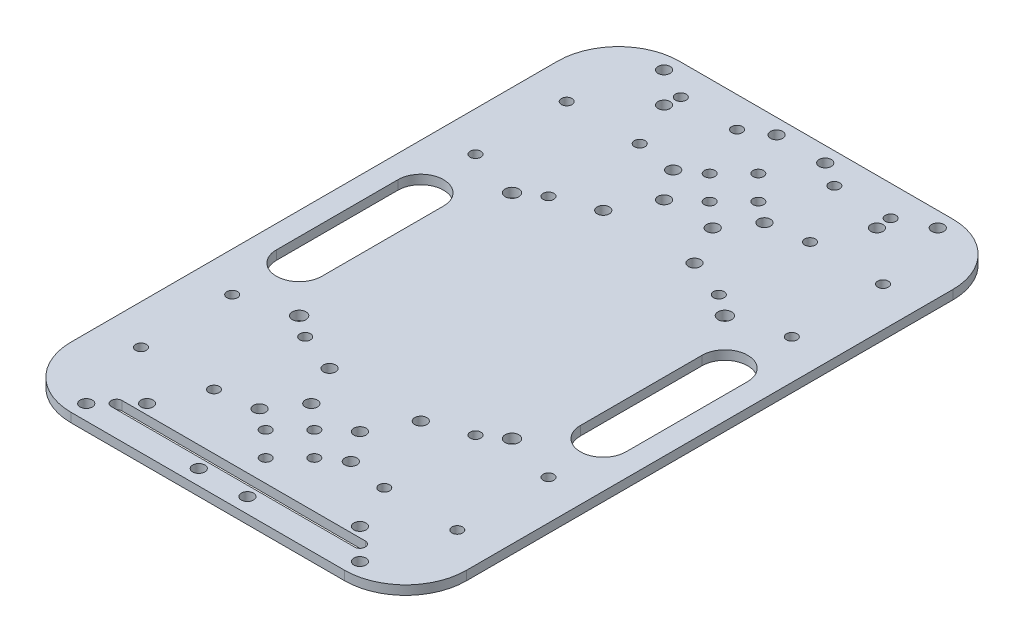
SolidWorks part; units mm, degrees
ref_plane "前视基准面" through (0, 0, 0) normal (0, 0, 1) x (1, 0, 0)
ref_plane "上视基准面" through (0, 0, 0) normal (0, 1, 0) x (1, 0, 0)
ref_plane "右视基准面" through (0, 0, 0) normal (1, 0, 0) x (0, 0, -1)
other "Configuration Table"
sketch "草图1" plane through (0, 0, 0) normal (0, 1, 0) x (1, 0, 0)
  line L0 (-40, -90) -> (40, -90) construction
  line L1 (-65, -100) -> (65, -100)
  line L2 (-65, -100) -> (-65, 100)
  line L3 (-65, 100) -> (65, 100)
  line L4 (65, -100) -> (65, 100)
  line L5 (-65, -100) -> (65, 100) construction
  line L6 (-65, 100) -> (65, -100) construction
  line L7 (-40, -88.25) -> (40, -88.25)
  line L8 (-40, -91.75) -> (40, -91.75)
  line L9 (50, -20) -> (50, 20) construction
  line L10 (42.5, -20) -> (42.5, 20)
  line L11 (57.5, -20) -> (57.5, 20)
  line L12 (-50, -20) -> (-50, 20) construction
  line L13 (-57.5, -20) -> (-57.5, 20)
  line L14 (-42.5, -20) -> (-42.5, 20)
  line L15 (0, 100) -> (0, -100) construction
  line L16 (-65, 0) -> (65, 0) construction
  circle A0 centre (52, -70) radius 1.75
  circle A1 centre (52, -40) radius 1.75
  circle A2 centre (28, -40) radius 1.75
  circle A3 centre (28, -70) radius 1.75
  circle A4 centre (52, 40) radius 1.75
  circle A5 centre (52, 70) radius 1.75
  circle A6 centre (28, 70) radius 1.75
  circle A7 centre (28, 40) radius 1.75
  circle A8 centre (-28, 40) radius 1.75
  circle A9 centre (-28, 70) radius 1.75
  circle A10 centre (-52, 70) radius 1.75
  circle A11 centre (-52, 40) radius 1.75
  circle A12 centre (-28, -70) radius 1.75
  circle A13 centre (-28, -40) radius 1.75
  circle A14 centre (-52, -40) radius 1.75
  circle A15 centre (-52, -70) radius 1.75
  circle A16 centre (35, -35) radius 2.25
  circle A17 centre (-35, -35) radius 2.25
  circle A18 centre (-35, 35) radius 2.25
  circle A19 centre (35, 35) radius 2.25
  circle A20 centre (16, 90) radius 1.75
  circle A21 centre (-16, 90) radius 1.75
  circle A22 centre (-34.5, 90) radius 1.75
  circle A25 centre (34.5, 90) radius 1.75
  circle A26 centre (-8, 73) radius 1.75
  circle A29 centre (0, 65) radius 1.75
  circle A31 centre (0, 81) radius 1.75
  circle A34 centre (8, 73) radius 1.75
  circle A35 centre (-8, -73) radius 1.75
  circle A36 centre (0, -81) radius 1.75
  circle A37 centre (0, -65) radius 1.75
  circle A38 centre (8, -73) radius 1.75
  arc A39 (-40, -88.25) -> (-40, -91.75) centre (-40, -90) ccw
  arc A40 (40, -91.75) -> (40, -88.25) centre (40, -90) ccw
  arc A41 (42.5, -20) -> (57.5, -20) centre (50, -20) ccw
  arc A42 (57.5, 20) -> (42.5, 20) centre (50, 20) ccw
  arc A43 (-57.5, -20) -> (-42.5, -20) centre (-50, -20) ccw
  arc A44 (-42.5, 20) -> (-57.5, 20) centre (-50, 20) ccw
  circle A45 centre (15, 45) radius 2
  circle A46 centre (-15, 45) radius 2
  circle A47 centre (-15, 68) radius 2
  circle A48 centre (15, 68) radius 2
  circle A53 centre (15, -68) radius 2
  circle A54 centre (-15, -68) radius 2
  circle A55 centre (-15, -45) radius 2
  circle A56 centre (15, -45) radius 2
  circle A57 centre (35, 85) radius 2
  circle A58 centre (-35, 85) radius 2
  circle A59 centre (35, -85) radius 2
  circle A60 centre (-35, -85) radius 2
  circle A61 centre (8, -58) radius 2
  circle A62 centre (8, -95) radius 2
  circle A63 centre (45, -95) radius 2
  circle A64 centre (-45, -95) radius 2
  circle A65 centre (-8, -95) radius 2
  circle A66 centre (-8, -58) radius 2
  circle A67 centre (45, 95) radius 2
  circle A68 centre (8, 95) radius 2
  circle A69 centre (-8, 95) radius 2
  circle A70 centre (-45, 95) radius 2
  circle A71 centre (8, 58) radius 2
  circle A72 centre (-8, 58) radius 2
  point P0 (0, 0)
  point P77 (0, -90)
  point P91 (50, 0)
  point P99 (-50, 0)
  dimension "D3" = 3.5
  dimension "D4" = 3.5
  dimension "D5" = 3.5
  dimension "D6" = 3.5
  dimension "D12" = 4.5
  dimension "D24" = 3.5
  dimension "D25" = 3.5
  dimension "D26" = 3.5
  dimension "D27" = 3.5
  dimension "D32" = 3.5
  dimension "D33" = 3.5
  dimension "D34" = 3.5
  dimension "D35" = 3.5
  dimension "D40" = 4.5
  dimension "D41" = 4.5
  dimension "D42" = 4.5
  dimension "D43" = 3.5
  dimension "D44" = 3.5
  dimension "D45" = 3.5
  dimension "D46" = 3.5
  dimension "D63" = 3.5
  dimension "D64" = 3.5
  dimension "D65" = 3.5
  dimension "D66" = 3.5
  dimension "D75" = 3.5
  dimension "D76" = 3.5
  dimension "D77" = 3.5
  dimension "D78" = 3.5
  dimension "D87" = 3.5
  dimension "D88" = 3.5
  dimension "D89" = 3.5
  dimension "D90" = 3.5
  dimension "D102" = 80
  dimension "D111" = 4
  dimension "D112" = 4
  dimension "D113" = 4
  dimension "D114" = 4
  dimension "D129" = 4
  dimension "D130" = 4
  dimension "D131" = 4
  dimension "D132" = 4
  dimension "D135" = 4
  dimension "D136" = 4
  dimension "D141" = 4
  dimension "D142" = 4
  dimension "D147" = 4
  dimension "D148" = 4
  dimension "D149" = 4
  dimension "D1" = 130
  dimension "D2" = 200
  dimension "D7" = 24
  dimension "D8" = 24
  dimension "D9" = 30
  dimension "D10" = 30
  dimension "D11" = 13
  dimension "D13" = 70
  dimension "D14" = 70
  dimension "D15" = 70
  dimension "D16" = 70
  dimension "D17" = 30
  dimension "D18" = 0
  dimension "D19" = 0
  dimension "D20" = 30
  dimension "D21" = 13
  dimension "D22" = 0
  dimension "D23" = 24
  dimension "D28" = 0
  dimension "D29" = 0
  dimension "D30" = 30
  dimension "D31" = 0
  dimension "D36" = 35
  dimension "D37" = 0
  dimension "D38" = 35
  dimension "D39" = 0
  dimension "D47" = 24
  dimension "D48" = 30
  dimension "D49" = 30
  dimension "D50" = 13
  dimension "D51" = 0
  dimension "D52" = 0
  dimension "D53" = 0
  dimension "D54" = 0
  dimension "D55" = 30
  dimension "D56" = 13
  dimension "D57" = 0
  dimension "D58" = 24
  dimension "D59" = 30
  dimension "D60" = 0
  dimension "D61" = 0
  dimension "D62" = 0
  dimension "D67" = 32
  dimension "D68" = 69
  dimension "D69" = 10
  dimension "D70" = 10
  dimension "D71" = 16
  dimension "D72" = 34.5
  dimension "D73" = 0
  dimension "D74" = 0
  dimension "D79" = 16
  dimension "D80" = 16
  dimension "D81" = 0
  dimension "D82" = 0
  dimension "D83" = 8
  dimension "D84" = 8
  dimension "D85" = 65
  dimension "D86" = 8
  dimension "D91" = 16
  dimension "D92" = 16
  dimension "D93" = 8
  dimension "D94" = 8
  dimension "D95" = 0
  dimension "D96" = 8
  dimension "D97" = 65
  dimension "D98" = 0
  dimension "D99" = 3.5
  dimension "D100" = 0
  dimension "D101" = 10
  dimension "D103" = 0
  dimension "D104" = 40
  dimension "D105" = 15
  dimension "D106" = 15
  dimension "D107" = 0
  dimension "D108" = 15
  dimension "D109" = 40
  dimension "D110" = 15
  dimension "D115" = 30
  dimension "D116" = 0
  dimension "D117" = 0
  dimension "D118" = 23
  dimension "D119" = 0
  dimension "D120" = 15
  dimension "D121" = 45
  dimension "D122" = 0
  dimension "D123" = 30
  dimension "D124" = 23
  dimension "D125" = 45
  dimension "D126" = 0
  dimension "D127" = 0
  dimension "D128" = 0
  dimension "D133" = 15
  dimension "D134" = 0
  dimension "D137" = 70
  dimension "D138" = 0
  dimension "D139" = 35
  dimension "D140" = 15
  dimension "D143" = 0
  dimension "D144" = 15
  dimension "D145" = 70
  dimension "D146" = 35
  dimension "D150" = 0
  dimension "D151" = 0
  dimension "D152" = 8
  dimension "D153" = 37
  dimension "D154" = 37
  dimension "D155" = 5
extrude "凸台-拉伸2" add sketch "草图1" along normal blind 3 contours L2 L1 L4 L3 | A11 | A18 | A8 | A10 | A9 | A22 | A21 | A20 | A25 | A6 | A31 | A26 | A34 | A29 | A5 | A4 | A7 | A19 | A1 | A16 | A2 | A0 | A3 | A37 | A35 | A38 | A36 | A13 | A17 | A14 | A15 | A12 | L7 A40 L8 A39 | A46 | A47 | A48 | A45 | A56 | A55 | A53 | A54 | A57 | A58 | A59 | A60 | A63 | A62 | A61 | A65 | A64 | A66 | A68 | A67 | A71 | A72 | A69 | A70 | L11 A41 L10 A42 | L13 A44 L14 A43
fillet "圆角1" radius 20 1 edges at (65, 1.5, 100)
fillet "圆角2" radius 20 1 edges at (-65, 1.5, 100)
fillet "圆角3" radius 20 1 edges at (-65, 1.5, -100)
fillet "圆角4" radius 20 1 edges at (65, 1.5, -100)
